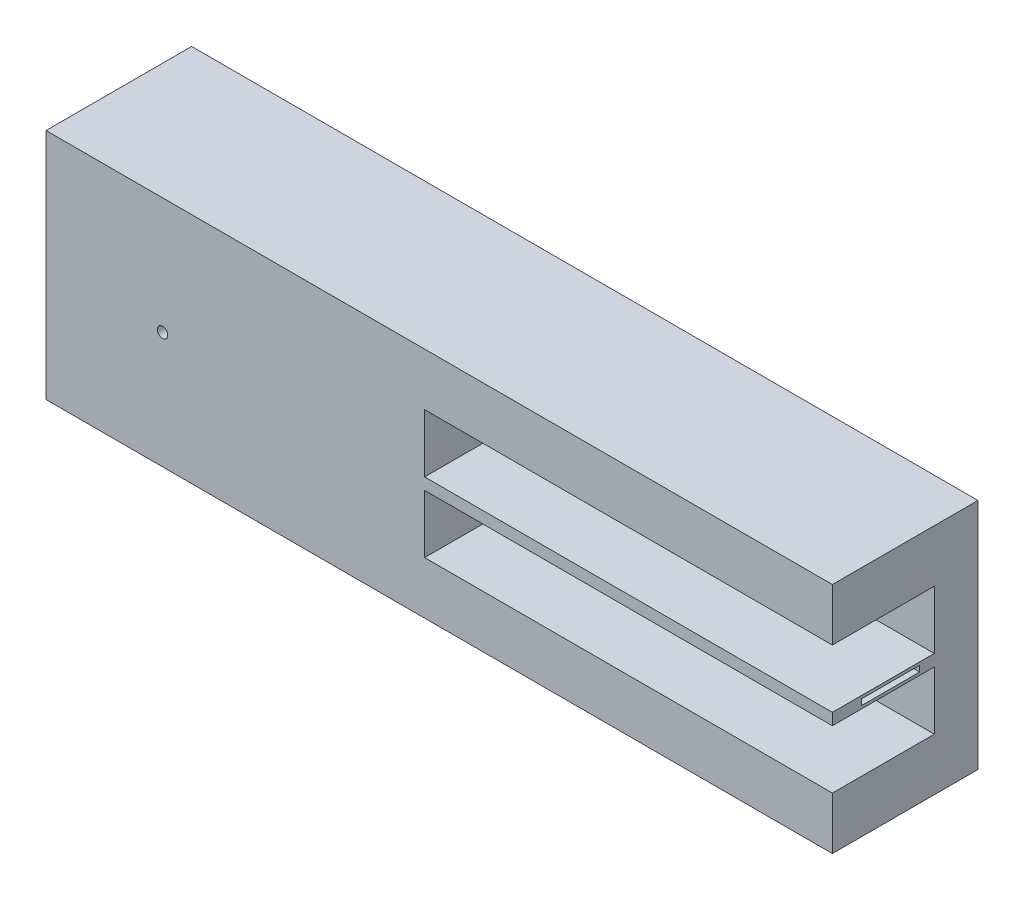
SolidWorks part; units mm, degrees
other "channel feature"
ref_plane "Front Plane" through (0, 0, 0) normal (1, 0, 0) x (0, 1, 0)
ref_plane "Top Plane" through (0, 0, 0) normal (0, 0, 1) x (0, 1, 0)
ref_plane "Right Plane" through (0, 0, 0) normal (0, 1, 0) x (-1, 0, 0)
sketch "guide" plane through (0, 0, 0) normal (0, 1, 0) x (-1, 0, 0)
  line L0 (-15, 0) -> (0, 0)
  line L1 (0, 0) -> (4, 0)
  line L2 (4, 0) -> (6, 0)
  arc A0 (6, 0) -> (8, 2) centre (6, 2) ccw
  point P7 (0, 0)
  point P8 (0, 0)
  point P9 (0, 0)
  point P10 (0, 0)
  point P11 (0, 0)
  dimension "D2" = 2
  dimension "D4" = 2
  dimension "D1" = 15
  dimension "D3" = 4
sketch "elec_ch_sketch" plane through (0, 0, 0) normal (1, 0, 0) x (0, 1, 0)
  line L1 (-0.1, -1) -> (0.1, -1)
  line L2 (-0.1, -1) -> (-0.1, 1)
  line L3 (-0.1, 1) -> (0.1, 1)
  line L4 (0.1, -1) -> (0.1, 1)
  line L5 (-0.1, -1) -> (0.1, 1) construction
  line L6 (-0.1, 1) -> (0.1, -1) construction
  point P0 (0, 0)
  dimension "D1" = 0.2
  dimension "D2" = 2
ref_plane "Plane1" through (-4, 0, 0) normal (1, 0, 0) x (0, 0, -1)
sketch "Sketch2" plane through (-4, 0, 0) normal (1, 0, 0) x (0, 0, -1)
  circle A0 centre (0, 0) radius 0.18
  dimension "D1" = 0.36
sweep "Sweep2" add profiles "elec_ch_sketch" path "guide"
sweep "Sweep3" add profiles "Sketch2" path "guide<3>"
sketch "guide<3>" plane through (0, 0, 0) normal (0, 1, 0) x (-1, 0, 0) same geometry as "guide"
loft "Loft1" add profiles "Sketch2<3>", "elec_ch_sketch<3>" connector at (-4, -0.1736, 0.0475) connector at (0, -0.1, 1)
sketch "Sketch2<3>" plane through (-4, 0, 0) normal (1, 0, 0) x (0, 0, -1) same geometry as "Sketch2"
sketch "elec_ch_sketch<3>" plane through (0, 0, 0) normal (1, 0, 0) x (0, 1, 0) same geometry as "elec_ch_sketch"
sketch "Sketch3" plane through (-4, 0, 0) normal (1, 0, 0) x (0, 0, -1)
  line L0 (1, -0.1) -> (1, 0.1) construction
  line L5 (3, -4) -> (-2, -4)
  line L6 (3, -4) -> (3, 4)
  line L7 (3, 4) -> (-2, 4)
  line L8 (-2, -4) -> (-2, 4)
  line L9 (-2, 0.18) -> (-2, -0.18) construction
  point P4 (3, 0)
  point P5 (0, 0)
  point P7 (0, 0)
  dimension "D1" = 2
  dimension "D2" = 0
  dimension "D3" = 4
extrude "Boss-Extrude1" add sketch "Sketch3" along normal up to surface (19 mm away) and the other way blind 8 separate body up to face at (15, 0, 0)
combine bodies "Combine1" operation type subtract main body 108 bodies to subtract 107
sketch "Sketch5" plane through (0, 0, 2) normal (0, 0, 1) x (1, 0, 0)
  line L0 (15, -4) -> (15, 4) construction
  line L1 (1, -0.2) -> (15, -0.2)
  line L2 (1, -0.2) -> (1, -2.2)
  line L3 (1, -2.2) -> (15, -2.2)
  line L4 (15, -0.2) -> (15, -2.2)
  line L5 (1, 2.2) -> (15, 2.2)
  line L6 (1, 2.2) -> (1, 0.2)
  line L7 (1, 0.2) -> (15, 0.2)
  line L8 (15, 2.2) -> (15, 0.2)
  line L9 (1, 0.2) -> (1, 0) construction
  line L10 (1, 0) -> (1, -0.2) construction
  line L11 (0, 0.1) -> (0, -0.1) construction
  line L12 (0, 0.1) -> (0, -0.1) construction
  line L13 (15, 0.1) -> (0, 0.1) construction
  point P10 (0, 0)
  dimension "D1" = 1
  dimension "D2" = 2
  dimension "D3" = 0.1
extrude "Cut-Extrude1" cut sketch "Sketch5" against normal offset from surface (3.5 mm away) 0.5 up to face at (7.5, 0, -1) offset beyond the face yes
